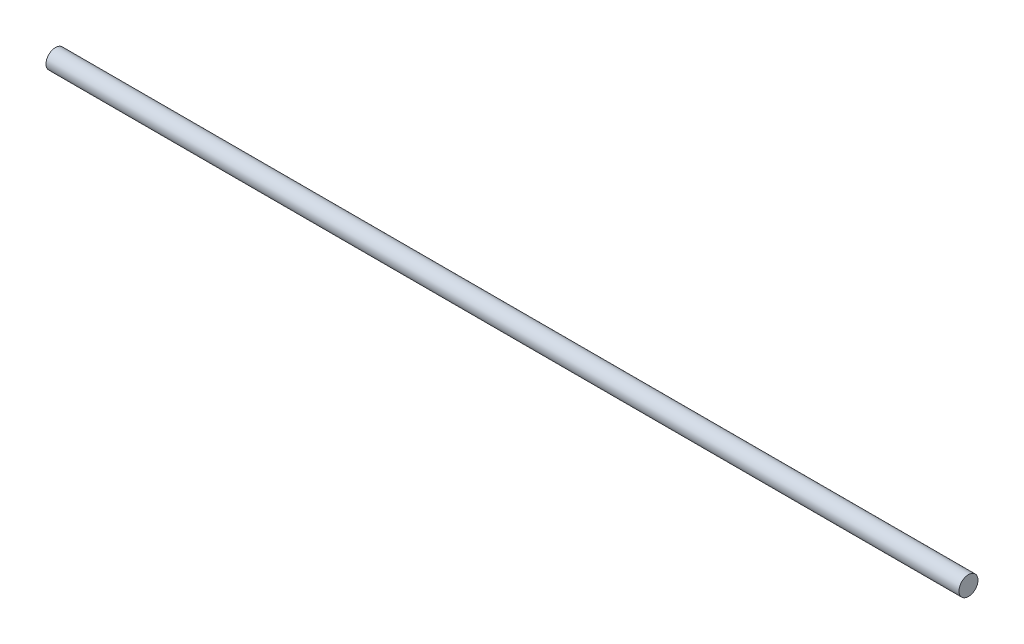
SolidWorks part; units mm, degrees
ref_plane "Front Plane" through (0, 0, 0) normal (0, 0, 1) x (1, 0, 0)
ref_plane "Top Plane" through (0, 0, 0) normal (0, 1, 0) x (1, 0, 0)
ref_plane "Right Plane" through (0, 0, 0) normal (1, 0, 0) x (0, 0, -1)
sketch "Sketch4" plane through (0, 0, 0) normal (1, 0, 0) x (0, 0, -1)
  circle A0 centre (0, 0) radius 3.81
  dimension "D1" = 7.62
extrude "Boss-Extrude2" add sketch "Sketch4" along normal blind 182.88 and the other way blind 182.88 separate body
ref_axis "Axle Axis" through (201.168, 0, 0) along (-1, 0, 0)
